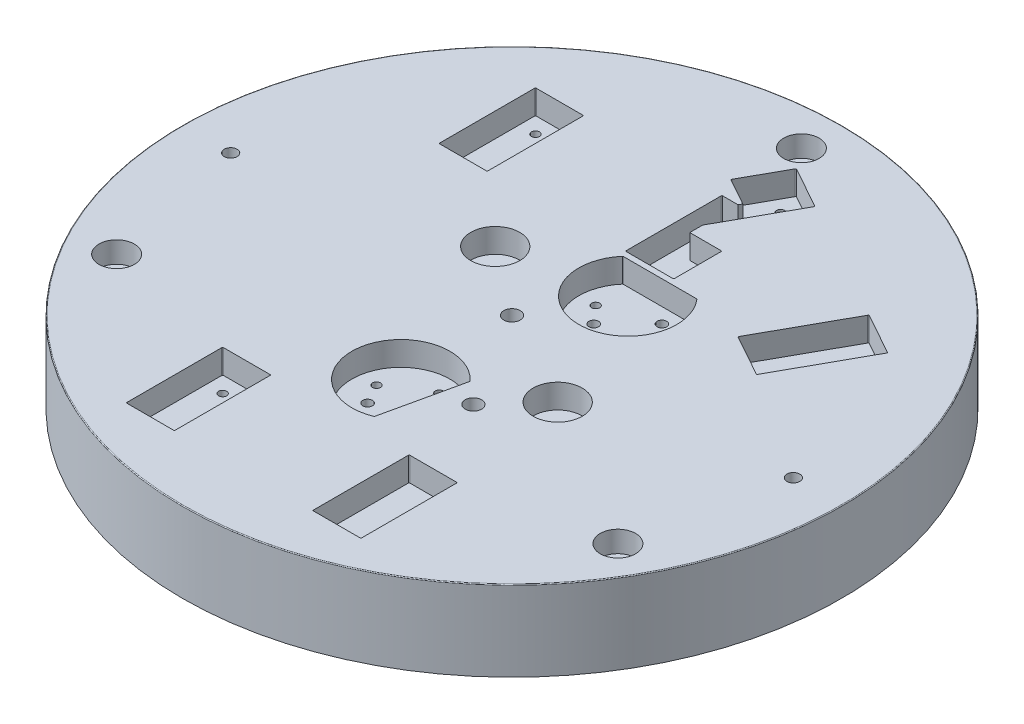
SolidWorks part; units mm, degrees
material "3003 Alloy"
ref_plane "Front Plane" through (0, 0, 0) normal (0, 0, 1) x (1, 0, 0)
ref_plane "Top Plane" through (0, 0, 0) normal (0, 1, 0) x (1, 0, 0)
ref_plane "Right Plane" through (0, 0, 0) normal (1, 0, 0) x (0, 0, -1)
sketch "Sketch1" plane through (0, 0, 0) normal (0, 1, 0) x (1, 0, 0)
  circle A0 centre (0, 0) radius 205
  dimension "D1" = 410
extrude "Boss-Extrude1" add sketch "Sketch1" along normal blind 50
sketch "Sketch2" plane through (0, 50, 0) normal (0, 1, 0) x (1, 0, 0)
  line L0 (-42.3277, 31.8965) -> (60.9712, -32.5462) construction
  line L2 (25.6946, 46.3547) -> (0, -69.1139) construction
  line L3 (22.5081, -48.5315) -> (11.6562, -97.2987)
  line L4 (2.6675, 66.3547) -> (48.7218, 66.3547)
  arc A1 (22.5081, -48.5315) -> (11.6562, -97.2987) centre (0, -69.1139) ccw
  arc A3 (2.6675, 66.3547) -> (48.7218, 66.3547) centre (25.6946, 46.3547) ccw
  circle A4 centre (-42.3277, 31.8965) radius 15.25
  circle A5 centre (60.9712, -32.5462) radius 15.25
  point P15 (0, 0)
  point P39 (250, 0)
  dimension "D3" = 61
  dimension "D6" = 20
  dimension "D10" = 61
  dimension "D11" = 69.1139
  dimension "D13" = 30.5
  dimension "D2" = 42.3277
  dimension "D4" = 31.8965
  dimension "D15" = 30.5
  dimension "D5" = 25.6946
  dimension "D7" = 46.3547
  dimension "D8" = 32.5462
  dimension "D9" = 60.9712
  dimension "D14" = 17.5
extrude "Cut-Extrude1" cut sketch "Sketch2" against normal blind 15
sketch "Sketch3" plane through (0, 50, 0) normal (0, 1, 0) x (1, 0, 0)
  line L57 (43.1123, -107.1139) -> (73.1123, -107.1139)
  line L92 (110.8144, 111.2209) -> (119.5606, 106.3728)
  line L93 (110.8144, 111.2209) -> (81.726, 58.7436)
  line L94 (81.726, 58.7436) -> (107.9646, 44.1994)
  line L95 (107.9646, 44.1994) -> (137.053, 96.6767)
  line L96 (137.053, 96.6767) -> (110.8144, 111.2209)
  line L97 (-85.3277, 129.8965) -> (-115.3277, 129.8965)
  line L98 (-115.3277, 129.8965) -> (-115.3277, 69.8965)
  line L99 (-115.3277, 69.8965) -> (-85.3277, 69.8965)
  line L100 (-85.3277, 129.8965) -> (-85.3277, 69.8965)
  line L104 (73.1123, -107.1139) -> (73.1123, -167.1139)
  line L107 (73.1123, -167.1139) -> (43.1123, -167.1139)
  line L108 (-42.8877, -107.1139) -> (-72.8877, -107.1139)
  line L109 (-72.8877, -107.1139) -> (-72.8877, -167.1139)
  line L110 (-72.8877, -167.1139) -> (-42.8877, -167.1139)
  line L111 (-42.8877, -107.1139) -> (-42.8877, -167.1139)
  line L112 (43.1123, -107.1139) -> (43.1123, -167.1139)
  line L113 (9.3583, 167.4584) -> (35.597, 152.9142)
  line L114 (0.6723, 129.8965) -> (10.6723, 129.8965)
  line L116 (0.6723, 69.8965) -> (30.6723, 69.8965)
  line L117 (30.6723, 99.8965) -> (30.6723, 69.8965)
  line L118 (35.597, 152.9142) -> (10.6723, 107.9486)
  line L120 (-5.1859, 141.2198) -> (9.3583, 167.4584)
  line L121 (30.6723, 99.8965) -> (10.6723, 99.8965)
  line L122 (10.6723, 99.8965) -> (10.6723, 107.9486)
  line L123 (10.6723, 129.8965) -> (11.7464, 131.8342)
  line L124 (-5.1859, 141.2198) -> (11.7464, 131.8342)
  line L125 (0.6723, 129.8965) -> (0.6723, 69.8965)
  line L126 (81.726, 58.7436) -> (10.6723, 98.129) construction
  line L127 (10.6723, 129.8965) -> (10.6723, 98.129) construction
  point P0 (0, 0)
  point P57 (0, 0)
  dimension "D2" = 81.726
  dimension "D3" = 10
  dimension "D4" = 58.7436
  dimension "D5" = 30
  dimension "D6" = 107.9646
  dimension "D7" = 111.2209
  dimension "D8" = 30
  dimension "D9" = 69.8965
  dimension "D10" = 60
  dimension "D11" = 30
  dimension "D12" = 30
  dimension "D13" = 30
  dimension "D14" = 30
  dimension "D16" = 86
  dimension "D17" = 20
  dimension "D18" = 30
  dimension "D19" = 60
  dimension "D15" = 30.6723
  dimension "D20" = 30
  dimension "D21" = 60
  dimension "D22" = 43.1123
  dimension "D23" = 107.1139
  dimension "D24" = 107.1139
  dimension "D25" = 42.8877
  dimension "D26" = 2.2155
  dimension "D27" = 85.3277
sketch "Sketch22" plane through (0, 50, 0) normal (0, 1, 0) x (1, 0, 0)
  line L2 (35.989, -60.0062) -> (-0.0148, 0.0248) construction
  circle A1 centre (-0.0148, 0.0248) radius 4
  circle A2 centre (35.989, -60.0062) radius 6
  dimension "D4" = 8
  dimension "D1" = 12
  dimension "D3" = 70
hole_wizard "M12 Tapped Hole3" positions "Sketch25" profile "Sketch26" tap size "M12" standard "ISO"
sketch "Sketch25" plane through (0, 50, 0) normal (0, 1, 0) x (1, 0, 0)
  point P0 (-0.0148, 0.0248)
sketch "Sketch26" plane through (-0.0148, 50, -0.0248) normal (1, 0, 0) x (0, 0, 1)
  line L0 (0, 0) -> (0, 29.25)
  line L1 (0, 29.25) -> (5.1, 26.1856)
  line L2 (5.1, 26.1856) -> (5.1, 0)
  line L5 (5.1, 0) -> (0, 0)
  line L10 (0, 29.25) -> (-5.1, 26.1856) construction
  line L11 (0, -6.35) -> (0, 107.95) construction
  dimension "Tap Drill Dia." = 10.2
  dimension "Tap Drill Depth" = 29.25
  dimension "Drill Angle" = 118
cosmetic thread "Hole Thread86" parameters "D1"=24, "D2"=12
extrude "Cut-Extrude2" cut sketch "Sketch3" against normal blind 15 contours L100 L97 L98 L99 | L95 L96 L92 L93 L94 | L111 L108 L109 L110 | L112 L107 L104 L57 | L117 L116 L125 L114 L123 L124 L120 L113 L118 L122 L121 region at (109.3895, 50, -77.7101) region at (-100.3277, 50, -99.8965) region at (-57.8877, 50, 137.1139)
sketch "Sketch27" plane through (0, 35, 0) normal (0, 1, 0) x (1, 0, 0)
  line L0 (137.053, 96.6767) -> (110.8144, 111.2209) construction
  line L1 (107.9646, 44.1994) -> (137.053, 96.6767) construction
  line L2 (30.6723, 99.8965) -> (30.6723, 69.8965) construction
  line L3 (81.726, 58.7436) -> (107.9646, 44.1994) construction
  line L4 (-115.3277, 129.8965) -> (-115.3277, 69.8965) construction
  line L5 (-85.3277, 129.8965) -> (-115.3277, 129.8965) construction
  line L6 (-115.3277, 69.8965) -> (-85.3277, 69.8965) construction
  line L7 (-42.8877, -107.1139) -> (-72.8877, -107.1139) construction
  line L8 (-72.8877, -107.1139) -> (-72.8877, -167.1139) construction
  line L9 (-72.8877, -167.1139) -> (-42.8877, -167.1139) construction
  line L10 (0.6723, 69.8965) -> (30.6723, 69.8965) construction
  line L11 (-72.8877, -107.1139) -> (-72.8877, -167.1139) construction
  line L12 (73.1123, -107.1139) -> (73.1123, -167.1139) construction
  line L13 (43.1123, -107.1139) -> (73.1123, -107.1139) construction
  line L14 (73.1123, -167.1139) -> (43.1123, -167.1139) construction
  line L15 (9.3583, 167.4584) -> (35.597, 152.9142) construction
  line L16 (-5.1859, 141.2198) -> (9.3583, 167.4584) construction
  circle A0 centre (123.4587, 92.7785) radius 3
  circle A1 centre (104.0665, 57.7937) radius 3
  circle A2 centre (-105.3277, 119.8965) radius 3
  circle A3 centre (-105.3277, 79.8965) radius 3
  circle A4 centre (-62.8877, -117.1139) radius 3
  circle A5 centre (-62.8877, -157.1139) radius 3
  circle A6 centre (63.1123, -117.1139) radius 3
  circle A7 centre (63.1123, -157.1139) radius 3
  circle A8 centre (20.6723, 79.8965) radius 3
  circle A9 centre (13.2565, 153.8642) radius 3
  dimension "D1" = 6
  dimension "D2" = 6
  dimension "D9" = 6
  dimension "D10" = 6
  dimension "D14" = 10
  dimension "D15" = 6
  dimension "D18" = 6
  dimension "D20" = 10
  dimension "D22" = 10
  dimension "D23" = 6
  dimension "D24" = 6
  dimension "D25" = 6
  dimension "D30" = 6
  dimension "D3" = 10
  dimension "D4" = 10
  dimension "D5" = 10
  dimension "D6" = 10
  dimension "D7" = 10
  dimension "D8" = 10
  dimension "D11" = 10
  dimension "D12" = 10
  dimension "D13" = 10
  dimension "D16" = 10
  dimension "D17" = 10
  dimension "D19" = 10
  dimension "D21" = 10
  dimension "D26" = 10
  dimension "D27" = 10
  dimension "D28" = 10
  dimension "D29" = 10
hole_wizard "M6 Tapped Hole3" positions "Sketch30" profile "Sketch31" tap size "M6" standard "ISO"
sketch "Sketch30" plane through (0, 35, 0) normal (0, 1, 0) x (1, 0, 0)
  point P0 (123.4587, 92.7785)
  point P3 (104.0665, 57.7937)
  point P6 (-105.3277, 119.8965)
  point P9 (-105.3277, 79.8965)
  point P12 (-62.8877, -117.1139)
  point P15 (-62.8877, -157.1139)
  point P18 (63.1123, -117.1139)
  point P21 (63.1123, -157.1139)
  point P24 (13.2565, 153.8642)
  point P27 (20.6723, 79.8965)
sketch "Sketch31" plane through (123.4587, 35, -92.7785) normal (1, 0, 0) x (0, 0, 1)
  line L0 (0, 0) -> (0, 15)
  line L1 (0, 15) -> (2.5, 13.4978)
  line L2 (2.5, 13.4978) -> (2.5, 0)
  line L5 (2.5, 0) -> (0, 0)
  line L10 (0, 15) -> (-2.5, 13.4978) construction
  line L11 (0, -6.35) -> (0, 107.95) construction
  dimension "Tap Drill Dia." = 5
  dimension "Tap Drill Depth" = 15
  dimension "Drill Angle" = 118
cosmetic thread "Hole Thread87" parameters "D1"=12, "D2"=6
cosmetic thread "Hole Thread88" parameters "D1"=12, "D2"=6
cosmetic thread "Hole Thread89" parameters "D1"=12, "D2"=6
cosmetic thread "Hole Thread90" parameters "D1"=12, "D2"=6
cosmetic thread "Hole Thread91" parameters "D1"=12, "D2"=6
cosmetic thread "Hole Thread92" parameters "D1"=12, "D2"=6
cosmetic thread "Hole Thread93" parameters "D1"=12, "D2"=6
cosmetic thread "Hole Thread94" parameters "D1"=12, "D2"=6
cosmetic thread "Hole Thread95" parameters "D1"=12, "D2"=6
cosmetic thread "Hole Thread96" parameters "D1"=12, "D2"=6
hole_wizard "M12 Tapped Hole2" positions "Sketch33" profile "Sketch34" tap size "M12" standard "ISO"
sketch "Sketch33" plane through (0, 50, 0) normal (0, 1, 0) x (1, 0, 0)
  point P0 (35.989, -60.0062)
sketch "Sketch34" plane through (35.989, 50, 60.0062) normal (1, 0, 0) x (0, 0, 1)
  line L0 (0, 0) -> (0, 29.25)
  line L1 (0, 29.25) -> (5.1, 26.1856)
  line L2 (5.1, 26.1856) -> (5.1, 0)
  line L5 (5.1, 0) -> (0, 0)
  line L10 (0, 29.25) -> (-5.1, 26.1856) construction
  line L11 (0, -6.35) -> (0, 107.95) construction
  dimension "Tap Drill Dia." = 10.2
  dimension "Tap Drill Depth" = 29.25
  dimension "Drill Angle" = 118
cosmetic thread "Hole Thread97" parameters "D1"=24, "D2"=12
sketch "Sketch35" plane through (0, 50, 0) normal (0, 1, 0) x (1, 0, 0)
  line L0 (-175.0148, 0.0248) -> (174.9852, 0.0248) construction
  circle A0 centre (-175.0148, 0.0248) radius 4
  circle A1 centre (174.9852, 0.0248) radius 4
  dimension "D1" = 8
  dimension "D2" = 350
extrude "Cut-Extrude4" cut sketch "Sketch35" against normal through all
sketch "Sketch36" plane through (0, 50, 0) normal (0, 1, 0) x (1, 0, 0)
  circle A0 centre (0, 180.0248) radius 11
  circle A1 centre (155.9061, -90.0124) radius 11
  circle A2 centre (-155.9061, -90.0124) radius 11
  point P10 (0, 0)
  dimension "D1" = 22
  dimension "D2" = 180
  dimension "D3" = 3
extrude "Cut-Extrude5" cut sketch "Sketch36" against normal blind 13.2
sketch "Sketch37" plane through (0, 36.8, 0) normal (0, 1, 0) x (1, 0, 0)
  circle A0 centre (0, 180.0248) radius 7
  circle A1 centre (155.9061, -90.0124) radius 7
  circle A2 centre (-155.9061, -90.0124) radius 7
  dimension "D1" = 14
extrude "Cut-Extrude6" cut sketch "Sketch37" against normal through all
fillet "Fillet1" radius 0.5 28 edges at (-115.3277, 42.5, -69.8965) (-115.3277, 42.5, -129.8965) (-85.3277, 42.5, -129.8965) (-85.3277, 42.5, -69.8965) (-42.8877, 42.5, 167.1139) (-42.8877, 42.5, 107.1139) (-72.8877, 42.5, 167.1139) (-72.8877, 42.5, 107.1139) (43.1123, 42.5, 107.1139) (43.1123, 42.5, 167.1139) (73.1123, 42.5, 107.1139) (73.1123, 42.5, 167.1139) (30.6723, 42.5, -99.8965) (30.6723, 42.5, -69.8965) (0.6723, 42.5, -69.8965) (0.6723, 42.5, -129.8965) (-5.1859, 42.5, -141.2198) (9.3583, 42.5, -167.4584) (35.597, 42.5, -152.9142) (137.053, 42.5, -96.6767) (110.8144, 42.5, -111.2209) (107.9646, 42.5, -44.1994) (81.726, 42.5, -58.7436) (0, 50, 205) (11.6562, 42.5, 97.2987) (22.5081, 42.5, 48.5315) (48.7218, 42.5, -66.3547) (2.6675, 42.5, -66.3547)
sketch "Sketch38" plane through (0, 35, 0) normal (0, 1, 0) x (1, 0, 0)
  line L0 (25.6946, 46.3547) -> (25.6946, 26.3547) construction
  line L1 (25.6946, 46.3547) -> (5.6946, 46.3547) construction
  circle A0 centre (25.6946, 26.3547) radius 3
  arc A1 (2.5166, 66.1797) -> (48.8726, 66.1797) centre (25.6946, 46.3547) ccw construction
  circle A2 centre (5.6946, 46.3547) radius 3
  circle A3 centre (25.6946, 66.3547) radius 3
  circle A4 centre (45.6946, 46.3547) radius 3
  dimension "D2" = 6
  dimension "D1" = 20
  dimension "D4" = 90
  dimension "D3" = 4
hole_wizard "M6 Tapped Hole4" positions "Sketch39" profile "Sketch40" tap size "M6" standard "ISO"
sketch "Sketch39" plane through (0, 35, 0) normal (0, 1, 0) x (1, 0, 0)
  point P0 (5.6946, 46.3547)
  point P3 (25.6946, 26.3547)
  point P6 (45.6946, 46.3547)
sketch "Sketch40" plane through (5.6946, 35, -46.3547) normal (1, 0, 0) x (0, 0, 1)
  line L0 (0, 0) -> (0, 15)
  line L1 (0, 15) -> (2.5, 13.4978)
  line L2 (2.5, 13.4978) -> (2.5, 0)
  line L5 (2.5, 0) -> (0, 0)
  line L10 (0, 15) -> (-2.5, 13.4978) construction
  line L11 (0, -6.35) -> (0, 107.95) construction
  dimension "Tap Drill Dia." = 5
  dimension "Tap Drill Depth" = 15
  dimension "Drill Angle" = 118
cosmetic thread "Hole Thread98" parameters "D1"=12, "D2"=6
cosmetic thread "Hole Thread99" parameters "D1"=12, "D2"=6
cosmetic thread "Hole Thread100" parameters "D1"=12, "D2"=6
sketch "Sketch43" plane through (0, 35, 0) normal (0, 1, 0) x (1, 0, 0)
  line L0 (0, -69.1139) -> (-29.7718, -62.4889) construction
  line L1 (11.713, -97.0433) -> (22.4513, -48.7868) construction
  arc A0 (22.3293, -48.3376) -> (11.4121, -97.3984) centre (0, -69.1139) ccw construction
  circle A1 centre (-19.5225, -64.7696) radius 3
  circle A2 centre (4.3442, -49.5914) radius 3
  arc A3 (22.3293, -48.3376) -> (11.4121, -97.3984) centre (0, -69.1139) ccw construction
  circle A4 centre (19.5225, -73.4581) radius 3
  circle A5 centre (-4.3442, -88.6364) radius 3
  point P22 (0, -69.1139)
  dimension "D1" = 6
  dimension "D2" = 20
  dimension "D3" = 4
hole_wizard "M6 Tapped Hole5" positions "Sketch44" profile "Sketch45" tap size "M6" standard "ISO"
sketch "Sketch44" plane through (0, 35, 0) normal (0, 1, 0) x (1, 0, 0)
  point P0 (-19.5225, -64.7696)
  point P3 (4.3442, -49.5914)
  point P6 (-4.3442, -88.6364)
sketch "Sketch45" plane through (-19.5225, 35, 64.7696) normal (1, 0, 0) x (0, 0, 1)
  line L0 (0, 0) -> (0, 15)
  line L1 (0, 15) -> (2.5, 13.4978)
  line L2 (2.5, 13.4978) -> (2.5, 0)
  line L5 (2.5, 0) -> (0, 0)
  line L10 (0, 15) -> (-2.5, 13.4978) construction
  line L11 (0, -6.35) -> (0, 107.95) construction
  dimension "Tap Drill Dia." = 5
  dimension "Tap Drill Depth" = 15
  dimension "Drill Angle" = 118
cosmetic thread "Hole Thread101" parameters "D1"=12, "D2"=6
cosmetic thread "Hole Thread102" parameters "D1"=12, "D2"=6
cosmetic thread "Hole Thread103" parameters "D1"=12, "D2"=6
sketch "Sketch46" plane through (0, 35, 0) normal (0, 1, 0) x (1, 0, 0)
  line L0 (-12.6572, -77.1634) -> (0, -69.1139) construction
  line L1 (0, -69.1139) -> (12.6572, -61.0644) construction
  line L2 (0, -69.1139) -> (-19.5225, -64.7696) construction
  line L3 (15.088, 35.7481) -> (25.6946, 46.3547) construction
  line L4 (25.6946, 46.3547) -> (36.3012, 56.9613) construction
  line L5 (5.6946, 46.3547) -> (25.6946, 46.3547) construction
  circle A2 centre (-12.6572, -77.1634) radius 3
  circle A3 centre (12.6572, -61.0644) radius 3
  arc A4 (22.3293, -48.3376) -> (11.4121, -97.3984) centre (0, -69.1139) ccw construction
  circle A6 centre (15.088, 35.7481) radius 3
  circle A7 centre (36.3012, 56.9613) radius 3
  arc A8 (2.5166, 66.1797) -> (48.8726, 66.1797) centre (25.6946, 46.3547) ccw construction
  arc A9 (2.5166, 66.1797) -> (48.8726, 66.1797) centre (25.6946, 46.3547) ccw construction
  dimension "D1" = 15
  dimension "D2" = 15
  dimension "D3" = 45
  dimension "D4" = 6
  dimension "D5" = 6
  dimension "D6" = 6
  dimension "D7" = 6
  dimension "D8" = 15
  dimension "D9" = 15
  dimension "D10" = 45
extrude "Cut-Extrude7" cut sketch "Sketch46" against normal blind 15
sketch "Sketch47" plane through (0, 35, 0) normal (0, 1, 0) x (1, 0, 0)
  circle A0 centre (60.9712, -32.5462) radius 7.3115
  circle A1 centre (-42.3277, 31.8965) radius 5.3299
hole_wizard "M12 Tapped Hole1" positions "Sketch48" profile "Sketch49" tap size "M12" standard "ISO"
sketch "Sketch48" plane through (0, 35, 0) normal (0, 1, 0) x (1, 0, 0)
  point P0 (-42.3277, 31.8965)
  point P3 (60.9712, -32.5462)
sketch "Sketch49" plane through (-42.3277, 35, -31.8965) normal (1, 0, 0) x (0, 0, 1)
  line L0 (0, 0) -> (0, 29.25)
  line L1 (0, 29.25) -> (5.1, 26.1856)
  line L2 (5.1, 26.1856) -> (5.1, 0)
  line L5 (5.1, 0) -> (0, 0)
  line L10 (0, 29.25) -> (-5.1, 26.1856) construction
  line L11 (0, -6.35) -> (0, 107.95) construction
  dimension "Tap Drill Dia." = 10.2
  dimension "Tap Drill Depth" = 29.25
  dimension "Drill Angle" = 118
cosmetic thread "Hole Thread104" parameters "D1"=24, "D2"=12
cosmetic thread "Hole Thread105" parameters "D1"=24, "D2"=12
